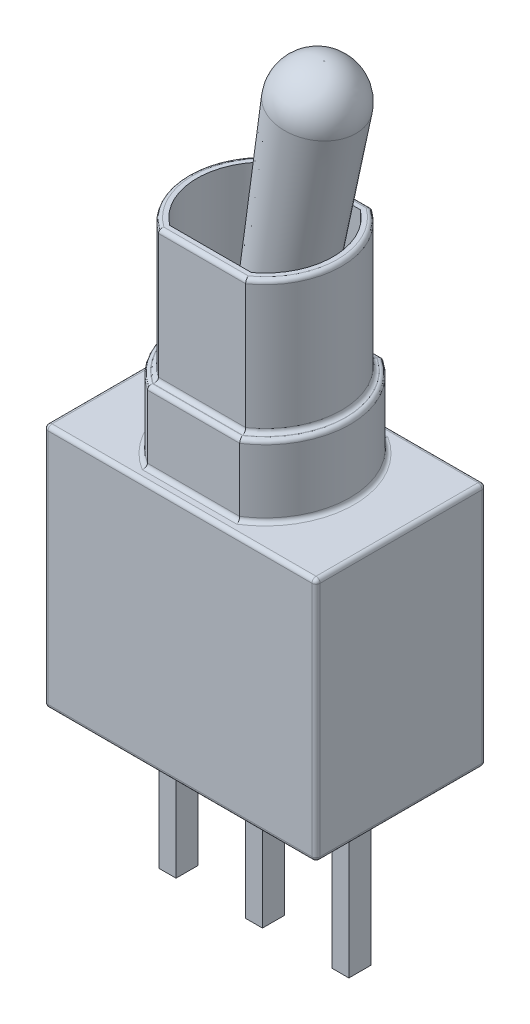
SolidWorks part; units mm, degrees
ref_plane "Front Plane" through (0, 0, 0) normal (0, 0, 1) x (1, 0, 0)
ref_plane "Top Plane" through (0, 0, 0) normal (0, 1, 0) x (1, 0, 0)
ref_plane "Right Plane" through (0, 0, 0) normal (1, 0, 0) x (0, 0, -1)
sketch "Sketch1" plane through (0, 0, 0) normal (0, 1, 0) x (1, 0, 0)
  line L1 (-4, 2.5) -> (4, 2.5)
  line L2 (-4, 2.5) -> (-4, -2.5)
  line L3 (-4, -2.5) -> (4, -2.5)
  line L4 (4, 2.5) -> (4, -2.5)
  line L5 (-4, 2.5) -> (4, -2.5) construction
  line L6 (-4, -2.5) -> (4, 2.5) construction
  point P0 (0, 0)
  dimension "D1" = 5
  dimension "D2" = 8
extrude "Boss-Extrude1" add sketch "Sketch1" along normal blind 7.2
sketch "Sketch2" plane through (0, 7.2, 0) normal (0, 1, 0) x (1, 0, 0)
  line L1 (1.3565, -2.1) -> (-1.3565, -2.1)
  line L2 (1.3565, -2.1) -> (1.3565, 2.1)
  line L3 (1.3565, 2.1) -> (-1.3565, 2.1)
  line L4 (-1.3565, -2.1) -> (-1.3565, 2.1)
  line L5 (1.3565, -2.1) -> (-1.3565, 2.1) construction
  line L6 (1.3565, 2.1) -> (-1.3565, -2.1) construction
  circle A0 centre (0, 0) radius 2.5
  dimension "D1" = 5
  dimension "D2" = 4.2
extrude "Boss-Extrude2" add sketch "Sketch2" along normal blind 2.1 contours L4 A0 | L4 L1 L2 L3 | L2 A0 region at (0, 7.2, 0) region at (1.8242, 7.2, 0) region at (-1.8242, 7.2, 0)
sketch "Sketch3" plane through (0, 9.3, 0) normal (0, 1, 0) x (1, 0, 0)
  line L4 (-1.2806, -1.85) -> (1.2806, -1.85)
  line L5 (1.2806, 1.85) -> (-1.2806, 1.85)
  line L6 (-1.2806, -1.85) -> (1.2806, -1.85)
  line L7 (1.2806, 1.85) -> (-1.2806, 1.85)
  arc A4 (-1.2806, 1.85) -> (-1.2806, -1.85) centre (0, 0) ccw
  arc A5 (1.2806, -1.85) -> (1.2806, 1.85) centre (0, 0) ccw
  arc A6 (-1.2806, 1.85) -> (-1.2806, -1.85) centre (0, 0) ccw
  arc A7 (1.2806, -1.85) -> (1.2806, 1.85) centre (0, 0) ccw
  dimension "D1" = 0.25
extrude "Boss-Extrude3" add sketch "Sketch3" along normal offset from surface (3.9 mm away) 6 up to face at (0, 7.2, 0) offset beyond the face yes
sketch "Sketch4" plane through (0, 13.2, 0) normal (0, 1, 0) x (1, 0, 0)
  line L4 (1.2, 1.6) -> (-1.2, 1.6)
  line L5 (-1.2, -1.6) -> (1.2, -1.6)
  line L6 (1.2, 1.6) -> (-1.2, 1.6)
  line L7 (-1.2, -1.6) -> (1.2, -1.6)
  arc A4 (-1.2, 1.6) -> (-1.2, -1.6) centre (0, 0) ccw
  arc A5 (1.2, -1.6) -> (1.2, 1.6) centre (0, 0) ccw
  arc A6 (-1.2, 1.6) -> (-1.2, -1.6) centre (0, 0) ccw
  arc A7 (1.2, -1.6) -> (1.2, 1.6) centre (0, 0) ccw
  dimension "D1" = 0.25
extrude "Cut-Extrude1" cut sketch "Sketch4" against normal blind 6
ref_plane "Plane1" through (0, 8.2, 0) normal (0, 1, 0) x (1, 0, 0)
ref_axis "Axis1" through (0, 8.2, -88.99) along (0, 0, 1)
ref_plane "Plane2" through (-1.4023, 0.2473, 0) normal (-0.9848, 0.1736, 0) x (0, 0, 1)
ref_plane "Plane3" through (1.4023, 7.9527, 0) normal (-0.1736, -0.9848, 0) x (0, 0, 1)
sketch "Sketch5" plane through (1.4023, 7.9527, 0) normal (-0.1736, -0.9848, 0) x (0, 0, 1)
  line L0 (3.025, 1.4239) -> (-3.025, 1.4239) construction
  line L1 (0, 4.8006) -> (0, -5.28) construction
  circle A0 centre (0, 1.4239) radius 0.9
  dimension "D1" = 1.8
ref_plane "Plane4" through (3.1388, 17.8008, 0) normal (-0.1736, -0.9848, 0) x (0, 0, 1)
sketch "Sketch6" plane through (3.1388, 17.8008, 0) normal (-0.1736, -0.9848, 0) x (0, 0, 1)
  circle A0 centre (0, 1.4239) radius 1.2
  dimension "D1" = 2.4
loft "Loft1" add profiles "Sketch6", "Sketch5" connector at (1.4738, 18.0944, 1.17) connector at (-0.0526, 8.2093, 0.8984)
fillet "Fillet1" radius 1.15 1 edges at (2.9183, 17.8397, 0)
sketch "Sketch7" plane through (0, 0, 0) normal (0, -1, 0) x (1, 0, 0)
  line L0 (-4, 0) -> (4, 0) construction
  line L1 (-4, -2.5) -> (-4, 2.5) construction
  line L2 (4, 2.5) -> (4, -2.5) construction
  line L3 (0, 2.5) -> (0, -2.5) construction
  line L4 (-4, 2.5) -> (4, 2.5) construction
  line L5 (4, -2.5) -> (-4, -2.5) construction
  line L6 (2.79, 0.325) -> (2.79, -0.325)
  line L7 (-0.25, 0.325) -> (0.25, 0.325)
  line L8 (-0.25, 0.325) -> (-0.25, -0.325)
  line L9 (-0.25, -0.325) -> (0.25, -0.325)
  line L10 (0.25, 0.325) -> (0.25, -0.325)
  line L11 (-0.25, 0.325) -> (0.25, -0.325) construction
  line L12 (-0.25, -0.325) -> (0.25, 0.325) construction
  line L13 (-2.79, 0.325) -> (-2.29, 0.325)
  line L14 (-2.79, 0.325) -> (-2.79, -0.325)
  line L15 (-2.79, -0.325) -> (-2.29, -0.325)
  line L16 (-2.29, 0.325) -> (-2.29, -0.325)
  line L17 (-2.79, 0.325) -> (-2.29, -0.325) construction
  line L18 (-2.79, -0.325) -> (-2.29, 0.325) construction
  line L19 (2.79, 0.325) -> (2.29, 0.325)
  line L20 (2.29, 0.325) -> (2.29, -0.325)
  line L21 (2.79, -0.325) -> (2.29, -0.325)
  point P12 (0, 0)
  point P18 (-2.54, 0)
  dimension "D1" = 0.65
  dimension "D2" = 0.5
  dimension "D3" = 2.54
extrude "Boss-Extrude4" add sketch "Sketch7" along normal blind 4.6
fillet "Fillet2" radius 0.12 28 edges at (0, 9.3, -2.1) (2.5, 9.3, 0) (0, 9.3, 2.1) (-2.5, 9.3, 0) (0, 9.3, 1.85) (2.25, 9.3, 0) (0, 9.3, -1.85) (-2.25, 9.3, 0) (-4, 0, 0) (-4, 3.6, -2.5) (0, 0, -2.5) (4, 3.6, -2.5) (4, 0, 0) (-4, 3.6, 2.5) (4, 3.6, 2.5) (0, 0, 2.5) (0, 7.2, 2.5) (-4, 7.2, 0) (0, 7.2, -2.5) (4, 7.2, 0) (0, 7.2, 2.1) (2.5, 7.2, 0) (0, 7.2, -2.1) (-2.5, 7.2, 0) (0, 13.2, 1.85) (-2.25, 13.2, 0) (0, 13.2, -1.85) (2.25, 13.2, 0)
